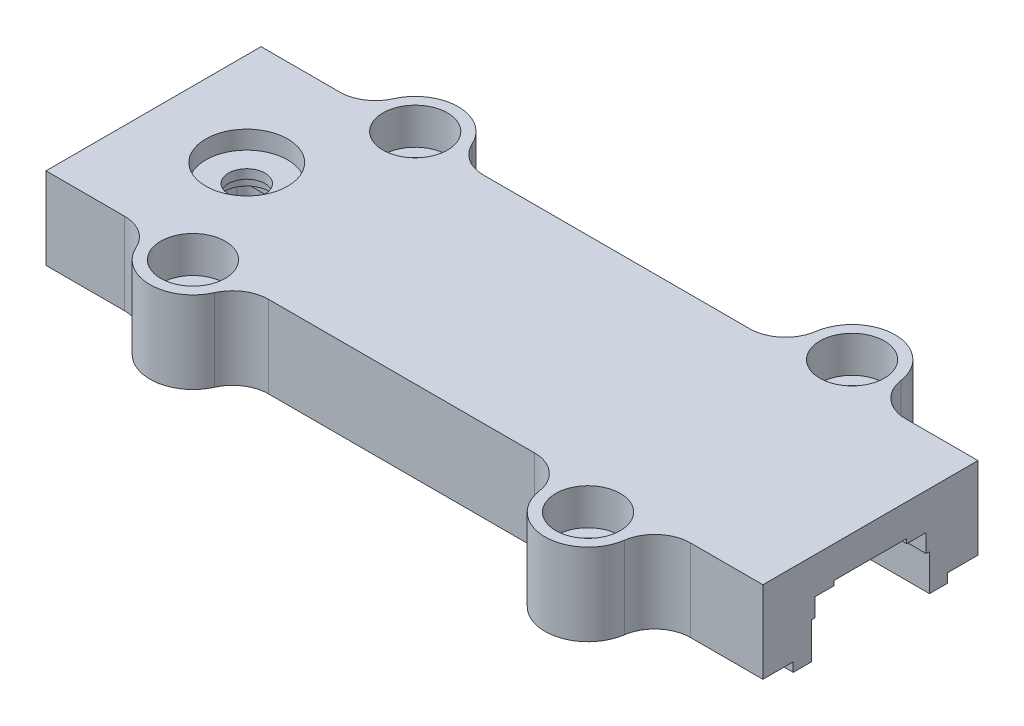
SolidWorks part; units mm, degrees
ref_plane "Front Plane" through (0, 0, 0) normal (0, 0, 1) x (1, 0, 0)
ref_plane "Top Plane" through (0, 0, 0) normal (0, 1, 0) x (1, 0, 0)
ref_plane "Right Plane" through (0, 0, 0) normal (1, 0, 0) x (0, 0, -1)
sketch "Sketch1" plane through (0, 0, 0) normal (0, 1, 0) x (1, 0, 0)
  line L1 (0, 15) -> (100, 15)
  line L2 (0, 15) -> (0, -15)
  line L3 (0, -15) -> (100, -15)
  line L4 (100, 15) -> (100, -15)
  point P4 (0, 0)
  dimension "D1" = 30
  dimension "D2" = 100
extrude "Boss-Extrude1" add sketch "Sketch1" along normal blind 12.7
sketch "Sketch2" plane through (100, 0, 0) normal (1, 0, 0) x (0, 0, -1)
  line L1 (-7.6, 0) -> (7.6, 0)
  line L2 (-7.6, 0) -> (-7.6, 7.62)
  line L3 (-7.6, 7.62) -> (7.6, 7.62)
  line L4 (7.6, 0) -> (7.6, 7.62)
  point P4 (0, 0)
  dimension "D1" = 15.2
  dimension "D2" = 7.62
extrude "Cut-Extrude1" cut sketch "Sketch2" against normal through all
sketch "Sketch3" plane through (100, 0, 0) normal (1, 0, 0) x (0, 0, -1)
  line L1 (-15, 0) -> (-7.6, 0) construction
  line L2 (7.6, 0) -> (15, 0) construction
  line L3 (-7.6, 0) -> (-8.235, 0)
  line L10 (7.6, 0) -> (7.6, 7.62) construction
  line L12 (7.6, 7.62) -> (-7.6, 7.62) construction
  line L13 (-7.6, 0) -> (-8.235, 0)
  line L14 (-7.6, 0) -> (-7.6, 5.08)
  line L15 (-7.6, 5.08) -> (-8.235, 5.08)
  line L16 (-8.235, 0) -> (-8.235, 5.08)
  line L17 (-7.6, 7.62) -> (-7.6, 0) construction
  line L18 (7.6, 0) -> (8.235, 0)
  line L19 (7.6, 0) -> (7.6, 5.08)
  line L20 (7.6, 5.08) -> (8.235, 5.08)
  line L21 (8.235, 0) -> (8.235, 5.08)
  line L22 (-5.06, 7.62) -> (5.06, 7.62)
  line L23 (-5.06, 7.62) -> (-5.06, 8.255)
  line L24 (-5.06, 8.255) -> (5.06, 8.255)
  line L25 (5.06, 7.62) -> (5.06, 8.255)
  line M1 (-15, 0) -> (-7.6, 0)
  line M2 (-7.6, 0) -> (-7.6, 7.62)
  line M3 (-7.6, 7.62) -> (7.6, 7.62)
  line M4 (7.6, 7.62) -> (7.6, 0)
  line M5 (7.6, 0) -> (15, 0)
  dimension "D5" = 0.635
  dimension "D6" = 2.54
  dimension "D7" = 0.635
  dimension "D8" = 2.54
  dimension "D9" = 0.635
  dimension "D10" = 2.54
  dimension "D11" = 2.54
extrude "Cut-Extrude2" cut sketch "Sketch3" against normal through all contours L16 L15 M1 M2 | L25 L24 L23 M3 | L21 L20 M5 M4 region at (100, 2.54, -7.9175) region at (100, 7.9375, 0) region at (100, 2.54, 7.9175)
sketch "Sketch4" plane through (0, 0, 0) normal (0, -1, 0) x (1, 0, 0)
  line L1 (0, -8.235) -> (5, -8.235)
  line L2 (0, -8.235) -> (0, 8.235)
  line L3 (0, 8.235) -> (5, 8.235)
  line L4 (5, -8.235) -> (5, 8.235)
  line L5 (0, -8.235) -> (100, -8.235) construction
  line L6 (0, 8.235) -> (100, 8.235) construction
  dimension "D1" = 5
extrude "Boss-Extrude2" add sketch "Sketch4" against normal up to next
fillet "Fillet7" radius 1.5875 2 edges at (5, 6.35, -7.6) (5, 6.35, 7.6)
fillet "Fillet8" radius 1.5875 2 edges at (5, 2.54, -8.235) (5, 2.54, 8.235)
sketch "Sketch9" plane through (0, 7.62, 0) normal (0, -1, 0) x (1, 0, 0)
  line L0 (5, -5.06) -> (100, -5.06) construction
  line L1 (5, 5.06) -> (24.05, 5.06)
  line L2 (5, 5.06) -> (5, -5.06)
  line L3 (5, -5.06) -> (24.05, -5.06)
  line L4 (24.05, 5.06) -> (24.05, -5.06)
  dimension "D1" = 19.05
extrude "Boss-Extrude3" add sketch "Sketch9" against normal up to next
sketch "Sketch7" plane through (0, 7.62, 0) normal (0, -1, 0) x (1, 0, 0)
  line L0 (0, -15) -> (0, 15) construction
  line L1 (5, -6.0125) -> (5, 6.0125) construction
  circle A0 centre (13, 0) radius 2.54
  point P6 (0, 0)
  dimension "D1" = 5.08
  dimension "D2" = 8
extrude "Cut-Extrude4" cut sketch "Sketch7" against normal through all
sketch "Sketch10" plane through (0, 7.62, 0) normal (0, -1, 0) x (1, 0, 0)
  circle A0 centre (13, 0) radius 3.175
  circle A3 centre (13, 0) radius 2.54 construction
  dimension "D1" = 6.35
extrude "Cut-Extrude6" cut sketch "Sketch10" against normal blind 1.27
sketch "Sketch8" plane through (0, 12.7, 0) normal (0, 1, 0) x (1, 0, 0)
  circle A0 centre (13, 0) radius 5.715
  dimension "D1" = 11.43
extrude "Cut-Extrude5" cut sketch "Sketch8" against normal blind 2.54
fillet "Fillet5" radius 1.5875 2 edges at (24.05, 7.9375, -5.06) (24.05, 7.9375, 5.06)
sketch "Sketch11" plane through (0, 12.7, 0) normal (0, 1, 0) x (1, 0, 0)
  line L0 (73, -15) -> (73.0221, -18.415)
  line L1 (85, -15) -> (85.0221, -18.415)
  line L4 (27, -15.5) -> (27, -15)
  line L5 (15, -15) -> (15, -15.5)
  line L8 (15, -15) -> (27, -15)
  line L9 (73, -15) -> (85, -15)
  line L11 (0, 15) -> (0, -15) construction
  line L13 (0, -15) -> (100, -15) construction
  arc A0 (73.0847, -19.2795) -> (84.9594, -19.2795) centre (79.0221, -18.415) ccw construction
  arc A2 (15, -15.5) -> (27, -15.5) centre (21, -15.5) ccw
  arc A3 (73.0221, -18.415) -> (85.0221, -18.415) centre (79.0221, -18.415) ccw
  dimension "D1" = 15
  dimension "D2" = 12
  dimension "D4" = 12
  dimension "D5" = 0.5
extrude "Boss-Extrude4" add sketch "Sketch11" against normal up to surface (12.7 mm away) up to face at (42.2517, 0, 0)
sketch "Sketch12" plane through (0, 12.7, 0) normal (0, 1, 0) x (1, 0, 0)
  circle A0 centre (21, -15.5) radius 4.5
  circle A1 centre (79.0221, -18.415) radius 4.5
  dimension "D1" = 9
extrude "Cut-Extrude7" cut sketch "Sketch12" against normal blind 5.08
sketch "Sketch13" plane through (0, 7.62, 0) normal (0, 1, 0) x (1, 0, 0)
  circle A0 centre (21, -15.5) radius 2.75
  circle A1 centre (79.0221, -18.415) radius 2.75
  dimension "D1" = 5.5
extrude "Cut-Extrude8" cut sketch "Sketch13" against normal through all
mirror "Mirror1" about plane through (0, 0, 0) normal (0, 0, 1) of "Boss-Extrude4", "Cut-Extrude7", "Cut-Extrude8"
fillet "Fillet6" radius 5 8 edges at (73, 6.35, 15) (85, 6.35, 15) (85, 6.35, -15) (73, 6.35, -15)
sketch "Sketch24" plane through (0, 0, 0) normal (0, -1, 0) x (1, 0, 0)
  line L0 (100, -10.775) -> (6.5875, -10.775)
  line L1 (2.46, -6.6475) -> (2.46, 6.6475)
  line L2 (6.5875, 10.775) -> (100, 10.775)
  line L12 (100, -15) -> (100, -8.235)
  line L13 (100, -8.235) -> (6.5875, -8.235)
  line L14 (5, -6.6475) -> (5, 6.6475)
  line L15 (6.5875, 8.235) -> (100, 8.235)
  line L16 (100, 8.235) -> (100, 15)
  line L17 (100, 15) -> (89.9073, 15)
  line L18 (68.1369, 15) -> (31.0374, 15)
  line L19 (10.9626, 15) -> (0, 15)
  line L20 (0, 15) -> (0, -15)
  line L21 (0, -15) -> (10.9626, -15)
  line L22 (31.0374, -15) -> (68.1369, -15)
  line L23 (89.9073, -15) -> (100, -15)
  line L24 (100, -15) -> (100, -10.775)
  line L25 (100, -8.235) -> (6.5875, -8.235) construction
  line L26 (5, -6.6475) -> (5, 6.6475) construction
  line L27 (6.5875, 8.235) -> (100, 8.235) construction
  line L28 (100, 10.775) -> (100, 15)
  line L29 (100, 15) -> (89.9073, 15)
  line L30 (68.1369, 15) -> (31.0374, 15)
  line L31 (10.9626, 15) -> (0, 15)
  line L32 (0, 15) -> (0, -15)
  line L33 (0, -15) -> (10.9626, -15)
  line L34 (31.0374, -15) -> (68.1369, -15)
  line L35 (89.9073, -15) -> (100, -15)
  arc A0 (2.46, -6.6475) -> (6.5875, -10.775) centre (6.5875, -6.6475) ccw
  arc A1 (6.5875, 10.775) -> (2.46, 6.6475) centre (6.5875, 6.6475) ccw
  arc A14 (5, -6.6475) -> (6.5875, -8.235) centre (6.5875, -6.6475) ccw
  arc A15 (6.5875, 8.235) -> (5, 6.6475) centre (6.5875, 6.6475) ccw
  arc A16 (84.9594, 19.2795) -> (89.9073, 15) centre (89.9073, 20) ccw
  arc A17 (84.9594, 19.2795) -> (73.0847, 19.2795) centre (79.0221, 18.415) ccw
  arc A18 (68.1369, 15) -> (73.0847, 19.2795) centre (68.1369, 20) ccw
  arc A19 (26.475, 17.9545) -> (31.0374, 15) centre (31.0374, 20) ccw
  arc A20 (26.475, 17.9545) -> (15.525, 17.9545) centre (21, 15.5) ccw
  arc A21 (10.9626, 15) -> (15.525, 17.9545) centre (10.9626, 20) ccw
  arc A22 (15.525, -17.9545) -> (10.9626, -15) centre (10.9626, -20) ccw
  arc A23 (15.525, -17.9545) -> (26.475, -17.9545) centre (21, -15.5) ccw
  arc A24 (31.0374, -15) -> (26.475, -17.9545) centre (31.0374, -20) ccw
  arc A25 (73.0847, -19.2795) -> (68.1369, -15) centre (68.1369, -20) ccw
  arc A26 (73.0847, -19.2795) -> (84.9594, -19.2795) centre (79.0221, -18.415) ccw
  arc A27 (89.9073, -15) -> (84.9594, -19.2795) centre (89.9073, -20) ccw
  arc A28 (5, -6.6475) -> (6.5875, -8.235) centre (6.5875, -6.6475) ccw construction
  arc A29 (6.5875, 8.235) -> (5, 6.6475) centre (6.5875, 6.6475) ccw construction
  arc A30 (84.9594, 19.2795) -> (89.9073, 15) centre (89.9073, 20) ccw
  arc A31 (84.9594, 19.2795) -> (73.0847, 19.2795) centre (79.0221, 18.415) ccw
  arc A32 (68.1369, 15) -> (73.0847, 19.2795) centre (68.1369, 20) ccw
  arc A33 (26.475, 17.9545) -> (31.0374, 15) centre (31.0374, 20) ccw
  arc A34 (26.475, 17.9545) -> (15.525, 17.9545) centre (21, 15.5) ccw
  arc A35 (10.9626, 15) -> (15.525, 17.9545) centre (10.9626, 20) ccw
  arc A36 (15.525, -17.9545) -> (10.9626, -15) centre (10.9626, -20) ccw
  arc A37 (15.525, -17.9545) -> (26.475, -17.9545) centre (21, -15.5) ccw
  arc A38 (31.0374, -15) -> (26.475, -17.9545) centre (31.0374, -20) ccw
  arc A39 (73.0847, -19.2795) -> (68.1369, -15) centre (68.1369, -20) ccw
  arc A40 (73.0847, -19.2795) -> (84.9594, -19.2795) centre (79.0221, -18.415) ccw
  arc A41 (89.9073, -15) -> (84.9594, -19.2795) centre (89.9073, -20) ccw
  dimension "D3" = 21.55
  dimension "D1" = 0
  dimension "D2" = 2.54
extrude "Cut-Extrude9" cut sketch "Sketch24" against normal blind 1.27
sketch "Sketch25" plane through (0, 7.62, 0) normal (0, -1, 0) x (1, 0, 0)
  line L0 (27.86, 6.3669) -> (27.86, 0.436) construction
  line L1 (5, -6.6475) -> (5, 6.6475) construction
  line L2 (6.5875, 7.6) -> (100, 7.6) construction
  line L3 (24.685, 7.6) -> (27.86, 7.6)
  line L4 (24.685, 7.6) -> (24.685, 5.06)
  line L5 (24.685, 5.06) -> (27.86, 5.06)
  line L6 (27.86, 7.6) -> (27.86, 5.06)
  line L7 (25.6375, 5.06) -> (100, 5.06) construction
  line L8 (6.5875, -7.6) -> (100, -7.6) construction
  line L9 (24.685, -7.6) -> (27.86, -7.6)
  line L10 (24.685, -7.6) -> (24.685, -5.06)
  line L11 (24.685, -5.06) -> (27.86, -5.06)
  line L12 (27.86, -7.6) -> (27.86, -5.06)
  line L13 (25.6375, -5.06) -> (100, -5.06) construction
  dimension "D1" = 22.86
  dimension "D2" = 3.175
extrude "Boss-Extrude5" add sketch "Sketch25" along normal blind 2.54
sketch "Sketch26" plane through (24.685, 0, 0) normal (-1, 0, 0) x (0, 0, 1)
  line L0 (7.6, 7.62) -> (5.06, 7.62) construction
  line L1 (5.06, 7.62) -> (5.06, 5.08) construction
  line L2 (5.06, 5.08) -> (7.6, 5.08) construction
  line L3 (7.6, 5.08) -> (7.6, 7.62) construction
  line L4 (-5.06, 7.62) -> (-7.6, 7.62) construction
  line L5 (-7.6, 7.62) -> (-7.6, 5.08) construction
  line L6 (-7.6, 5.08) -> (-5.06, 5.08) construction
  line L7 (-5.06, 5.08) -> (-5.06, 7.62) construction
  line L8 (7.6, 7.62) -> (5.06, 7.62)
  line L9 (5.06, 7.62) -> (5.06, 5.08)
  line L10 (5.06, 5.08) -> (7.6, 5.08)
  line L11 (7.6, 5.08) -> (7.6, 7.62)
  line L12 (-5.06, 7.62) -> (-7.6, 7.62)
  line L13 (-7.6, 7.62) -> (-7.6, 5.08)
  line L14 (-7.6, 5.08) -> (-5.06, 5.08)
  line L15 (-5.06, 5.08) -> (-5.06, 7.62)
extrude "Boss-Extrude6" add sketch "Sketch26" along normal up to next
sketch "Sketch31" plane through (100, 0, 0) normal (1, 0, 0) x (0, 0, -1)
  line L2 (7.6, 5.08) -> (7.7651, 5.08)
  line L3 (7.6, 5.08) -> (7.6, 7.62)
  line L4 (7.6, 7.62) -> (7.7651, 7.62)
  line L5 (7.7651, 5.08) -> (7.7651, 7.62)
  line L6 (-7.6, 5.08) -> (-7.7651, 5.08)
  line L7 (-7.6, 5.08) -> (-7.6, 7.62)
  line L8 (-7.6, 7.62) -> (-7.7651, 7.62)
  line L9 (-7.7651, 5.08) -> (-7.7651, 7.62)
  dimension "D1" = 0.1651
  dimension "D2" = 0.1651
extrude "adjust" cut sketch "Sketch31" against normal up to surface (72.14 mm away) up to face at (27.86, 6.35, -6.33)
fillet "Fillet9" radius 1.5875 4 edges at (5, 6.35, -5.06) (5, 6.35, 5.06) (27.86, 6.35, 7.7651) (27.86, 6.35, -7.7651)
sketch "Sketch27" plane through (0, 0, 0) normal (0, 1, 0) x (1, 0, 0)
  line L1 (-5.3987, 25.4) -> (108.9013, 25.4)
  line L2 (-5.3987, 25.4) -> (-5.3987, -25.4)
  line L3 (-5.3987, -25.4) -> (108.9013, -25.4)
  line L4 (108.9013, 25.4) -> (108.9013, -25.4)
  point P4 (-5.3987, 0)
  dimension "D1" = 50.8
  dimension "D2" = 114.3
sketch "Sketch28" plane through (0, 0, 0) normal (0, -1, 0) x (1, 0, 0)
  line L0 (0, 0) -> (-2.8235, 0) construction
sketch "Sketch29" plane through (0, 12.7, 0) normal (0, 1, 0) x (1, 0, 0)
  line L8 (0, 15) -> (0, -15)
  line L9 (0, -15) -> (10.9626, -15)
  line L10 (31.0374, -15) -> (68.1369, -15)
  line L11 (89.9073, -15) -> (100, -15)
  line L12 (100, -15) -> (100, 15)
  line L13 (100, 15) -> (89.9073, 15)
  line L14 (68.1369, 15) -> (31.0374, 15)
  line L15 (10.9626, 15) -> (0, 15)
  line L16 (0, 15) -> (0, -15)
  line L17 (0, -15) -> (10.9626, -15)
  line L18 (31.0374, -15) -> (68.1369, -15)
  line L19 (89.9073, -15) -> (100, -15)
  line L20 (100, -15) -> (100, 15)
  line L21 (100, 15) -> (89.9073, 15)
  line L22 (68.1369, 15) -> (31.0374, 15)
  line L23 (10.9626, 15) -> (0, 15)
  arc A12 (15.525, -17.9545) -> (10.9626, -15) centre (10.9626, -20) ccw
  arc A13 (15.525, -17.9545) -> (26.475, -17.9545) centre (21, -15.5) ccw
  arc A14 (31.0374, -15) -> (26.475, -17.9545) centre (31.0374, -20) ccw
  arc A15 (73.0847, -19.2795) -> (68.1369, -15) centre (68.1369, -20) ccw
  arc A16 (73.0847, -19.2795) -> (84.9594, -19.2795) centre (79.0221, -18.415) ccw
  arc A17 (89.9073, -15) -> (84.9594, -19.2795) centre (89.9073, -20) ccw
  arc A18 (84.9594, 19.2795) -> (89.9073, 15) centre (89.9073, 20) ccw
  arc A19 (84.9594, 19.2795) -> (73.0847, 19.2795) centre (79.0221, 18.415) ccw
  arc A20 (68.1369, 15) -> (73.0847, 19.2795) centre (68.1369, 20) ccw
  arc A21 (26.475, 17.9545) -> (31.0374, 15) centre (31.0374, 20) ccw
  arc A22 (26.475, 17.9545) -> (15.525, 17.9545) centre (21, 15.5) ccw
  arc A23 (10.9626, 15) -> (15.525, 17.9545) centre (10.9626, 20) ccw
  arc A24 (15.525, -17.9545) -> (10.9626, -15) centre (10.9626, -20) ccw
  arc A25 (15.525, -17.9545) -> (26.475, -17.9545) centre (21, -15.5) ccw
  arc A26 (31.0374, -15) -> (26.475, -17.9545) centre (31.0374, -20) ccw
  arc A27 (73.0847, -19.2795) -> (68.1369, -15) centre (68.1369, -20) ccw
  arc A28 (73.0847, -19.2795) -> (84.9594, -19.2795) centre (79.0221, -18.415) ccw
  arc A29 (89.9073, -15) -> (84.9594, -19.2795) centre (89.9073, -20) ccw
  arc A30 (84.9594, 19.2795) -> (89.9073, 15) centre (89.9073, 20) ccw
  arc A31 (84.9594, 19.2795) -> (73.0847, 19.2795) centre (79.0221, 18.415) ccw
  arc A32 (68.1369, 15) -> (73.0847, 19.2795) centre (68.1369, 20) ccw
  arc A33 (26.475, 17.9545) -> (31.0374, 15) centre (31.0374, 20) ccw
  arc A34 (26.475, 17.9545) -> (15.525, 17.9545) centre (21, 15.5) ccw
  arc A35 (10.9626, 15) -> (15.525, 17.9545) centre (10.9626, 20) ccw
  dimension "D1" = 0
sketch "Sketch30" plane through (0, 12.7, 0) normal (0, 1, 0) x (1, 0, 0)
  line L0 (100, 3.2852) -> (100, 15)
  line L1 (0, 15) -> (0, -15) construction
  line L3 (0, -3.0648) -> (0, -15)
  line L4 (46.1739, 15) -> (31.0374, 15)
  line L6 (52.5239, -15) -> (68.1369, -15)
  line L8 (0, 15) -> (0, -15)
  line L9 (0, -15) -> (10.9626, -15)
  line L10 (31.0374, -15) -> (68.1369, -15)
  line L11 (89.9073, -15) -> (100, -15)
  line L12 (100, -15) -> (100, 15)
  line L13 (100, 15) -> (89.9073, 15)
  line L14 (68.1369, 15) -> (31.0374, 15)
  line L15 (10.9626, 15) -> (0, 15)
  line L16 (0, 15) -> (0, 3.2852)
  line L17 (0, -15) -> (10.9626, -15)
  line L18 (31.0374, -15) -> (46.1739, -15)
  line L19 (89.9073, -15) -> (100, -15)
  line L20 (100, -15) -> (100, -3.0648)
  line L21 (100, 15) -> (89.9073, 15)
  line L22 (68.1369, 15) -> (52.5239, 15)
  line L23 (10.9626, 15) -> (0, 15)
  arc A12 (15.525, -17.9545) -> (10.9626, -15) centre (10.9626, -20) ccw
  arc A13 (15.525, -17.9545) -> (26.475, -17.9545) centre (21, -15.5) ccw
  arc A14 (31.0374, -15) -> (26.475, -17.9545) centre (31.0374, -20) ccw
  arc A15 (73.0847, -19.2795) -> (68.1369, -15) centre (68.1369, -20) ccw
  arc A16 (73.0847, -19.2795) -> (84.9594, -19.2795) centre (79.0221, -18.415) ccw
  arc A17 (89.9073, -15) -> (84.9594, -19.2795) centre (89.9073, -20) ccw
  arc A18 (84.9594, 19.2795) -> (89.9073, 15) centre (89.9073, 20) ccw
  arc A19 (84.9594, 19.2795) -> (73.0847, 19.2795) centre (79.0221, 18.415) ccw
  arc A20 (68.1369, 15) -> (73.0847, 19.2795) centre (68.1369, 20) ccw
  arc A21 (26.475, 17.9545) -> (31.0374, 15) centre (31.0374, 20) ccw
  arc A22 (26.475, 17.9545) -> (15.525, 17.9545) centre (21, 15.5) ccw
  arc A23 (10.9626, 15) -> (15.525, 17.9545) centre (10.9626, 20) ccw
  arc A24 (15.525, -17.9545) -> (10.9626, -15) centre (10.9626, -20) ccw
  arc A25 (15.525, -17.9545) -> (26.475, -17.9545) centre (21, -15.5) ccw
  arc A26 (31.0374, -15) -> (26.475, -17.9545) centre (31.0374, -20) ccw
  arc A27 (73.0847, -19.2795) -> (68.1369, -15) centre (68.1369, -20) ccw
  arc A28 (73.0847, -19.2795) -> (84.9594, -19.2795) centre (79.0221, -18.415) ccw
  arc A29 (89.9073, -15) -> (84.9594, -19.2795) centre (89.9073, -20) ccw
  arc A30 (84.9594, 19.2795) -> (89.9073, 15) centre (89.9073, 20) ccw
  arc A31 (84.9594, 19.2795) -> (73.0847, 19.2795) centre (79.0221, 18.415) ccw
  arc A32 (68.1369, 15) -> (73.0847, 19.2795) centre (68.1369, 20) ccw
  arc A33 (26.475, 17.9545) -> (31.0374, 15) centre (31.0374, 20) ccw
  arc A34 (26.475, 17.9545) -> (15.525, 17.9545) centre (21, 15.5) ccw
  arc A35 (10.9626, 15) -> (15.525, 17.9545) centre (10.9626, 20) ccw
  dimension "D2" = 6.35
  dimension "D3" = 6.35
  dimension "D1" = 0
equation "\"D11@Sketch3\"=\"D10@Sketch3\""
equation "\"D6@Sketch3\"=\"D10@Sketch3\""
equation "\"D8@Sketch3\"=\"D10@Sketch3\""
equation "\"D9@Sketch3\" = \"D5@Sketch3\""
equation "\"D7@Sketch3\"=\"D5@Sketch3\""
